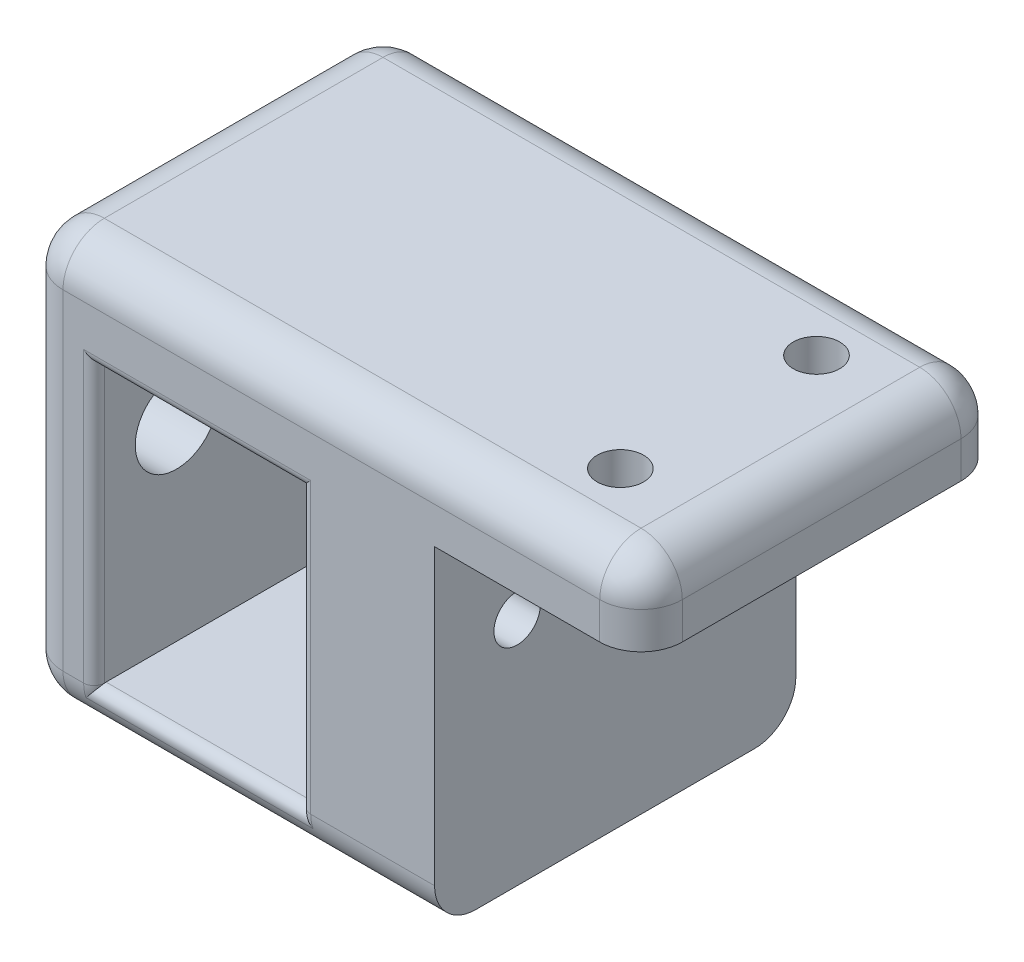
SolidWorks part; units mm, degrees
ref_plane "Front Plane" through (0, 0, 0) normal (0, 0, 1) x (1, 0, 0)
ref_plane "Top Plane" through (0, 0, 0) normal (0, 1, 0) x (1, 0, 0)
ref_plane "Right Plane" through (0, 0, 0) normal (1, 0, 0) x (0, 0, -1)
sketch "Sketch1" plane through (0, 0, 0) normal (0, 0, 1) x (1, 0, 0)
  line L1 (-10, -6) -> (10, -6)
  line L2 (-10, -6) -> (-10, 21)
  line L3 (-10, 21) -> (10, 21)
  line L4 (10, -6) -> (10, 21)
  line L7 (-17, -10) -> (23, -10)
  line L8 (-17, -10) -> (-17, 30)
  line L9 (-17, 30) -> (23, 30)
  line L10 (23, -10) -> (23, 30)
  point P0 (0, 0)
  point P6 (0, 0)
  dimension "D1" = 27
  dimension "D2" = 20
  dimension "D3" = 40
  dimension "D4" = 40
  dimension "D5" = 7
  dimension "D6" = 9
  dimension "D7" = 4
extrude "Boss-Extrude1" add sketch "Sketch1" along normal blind 30
sketch "Sketch2" plane through (0, 0, 0) normal (0, 0, -1) x (-1, 0, 0)
  line L5 (-10, 21) -> (10, -6) construction
  line L6 (-23, 30) -> (17, 30)
  line L8 (-23, 30) -> (-23, -10)
  line L9 (-23, -10) -> (17, -10)
  line L10 (17, 30) -> (17, -10)
  line L11 (10, 21) -> (-10, -6) construction
  circle A1 centre (0, 7.5) radius 2.25
  point P0 (0, 0)
  dimension "D1" = 4.5
extrude "Boss-Extrude2" add sketch "Sketch2" along normal blind 5
sketch "Sketch3" plane through (0, 30, 0) normal (0, 1, 0) x (1, 0, 0)
  line L7 (23, -30) -> (43, -30)
  line L8 (23, -30) -> (23, 5)
  line L9 (23, 5) -> (43, 5)
  line L10 (43, -30) -> (43, 5)
  circle A2 centre (33, -3) radius 2.25
  circle A3 centre (33, -22) radius 2.25
  dimension "D5" = 20
  dimension "D6" = 10
  dimension "D7" = 10
  dimension "D8" = 4.5
  dimension "D9" = 4.5
  dimension "D10" = 8
  dimension "D11" = 19
extrude "Boss-Extrude3" add sketch "Sketch3" against normal blind 7.55
sketch "Sketch4" plane through (23, 0, 0) normal (1, 0, 0) x (0, 0, -1)
  line L0 (5, 22.45) -> (-30, 22.45) construction
  line L1 (-30, -10) -> (-30, 22.45) construction
  circle A0 centre (-22, 12.45) radius 2.25
  circle A1 centre (-10, 12.45) radius 2.25
  dimension "D1" = 10
  dimension "D2" = 10
  dimension "D3" = 4.5
  dimension "D4" = 4.5
  dimension "D5" = 8
  dimension "D6" = 12
extrude "Cut-Extrude1" cut sketch "Sketch4" against normal through all
sketch "Sketch5" plane through (-17, 0, 0) normal (-1, 0, 0) x (0, 0, 1)
  circle A0 centre (10, 12.45) radius 4
  circle A1 centre (22, 12.45) radius 4
  dimension "D1" = 8
  dimension "D2" = 8
extrude "Cut-Extrude2" cut sketch "Sketch5" against normal blind 31
fillet "Fillet1" radius 4 11 edges at (13, 30, -5) (43, 26.225, -5) (43, 30, 12.5) (43, 26.225, 30) (13, 30, 30) (3, -10, -5) (3, -10, 30) (-17, -10, 12.5) (-17, 30, 12.5) (-17, 10, 30) (-17, 10, -5)
fillet "Fillet2" radius 1 4 edges at (0, 21, 30) (-10, 7.5, 30) (10, 7.5, 30) (0, -6, 30)
sketch "Sketch6" plane through (0, 0, -5) normal (0, 0, -1) x (-1, 0, 0)
  text T0 "L\r\n" font "Freestyle Script" height in points 72
extrude "Cut-Extrude3" cut sketch "Sketch6" against normal blind 1
